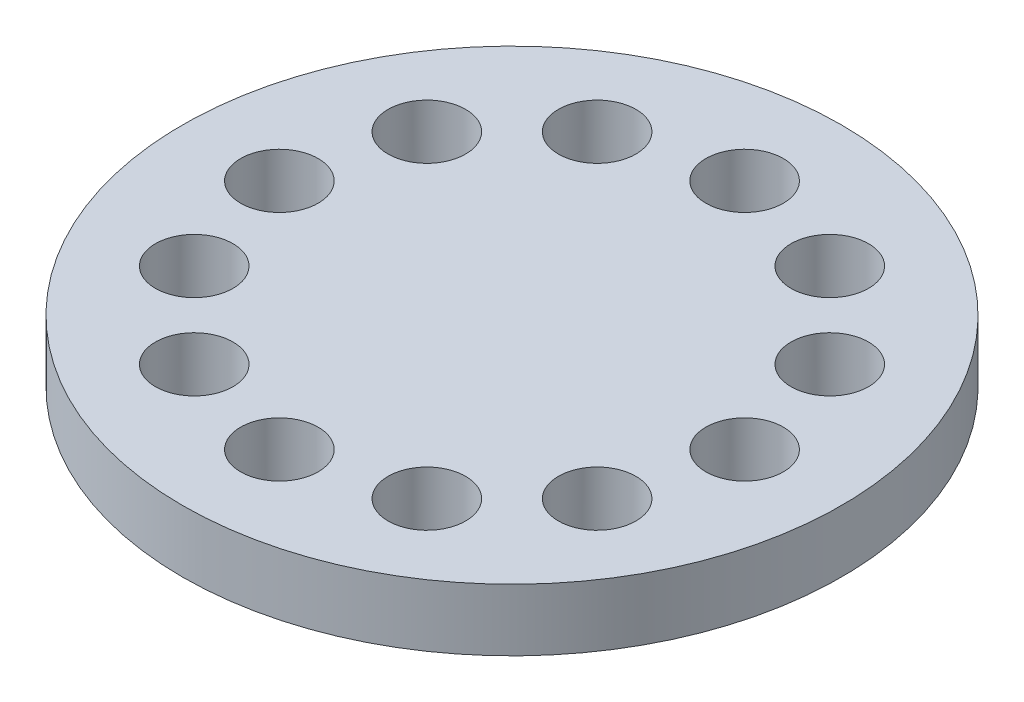
SolidWorks part; units mm, degrees
ref_plane "Front Plane" through (0, 0, 0) normal (0, 0, 1) x (1, 0, 0)
ref_plane "Top Plane" through (0, 0, 0) normal (0, 1, 0) x (1, 0, 0)
ref_plane "Right Plane" through (0, 0, 0) normal (1, 0, 0) x (0, 0, -1)
sketch "Sketch1" plane through (0, 0, 0) normal (0, 1, 0) x (1, 0, 0)
  circle A0 centre (0, 0) radius 13.4937
  dimension "D1" = 26.9875
extrude "Boss-Extrude1" add sketch "Sketch1" along normal blind 2.54
sketch "Sketch2" plane through (0, 2.54, 0) normal (0, 1, 0) x (1, 0, 0)
  line L0 (-9.525, 0) -> (0, 0) construction
  circle A0 centre (-9.525, 0) radius 1.5875
  dimension "D1" = 3.175
  dimension "D2" = 9.525
extrude "Cut-Extrude1" cut sketch "Sketch2" against normal through all both and the other way through all
ref_axis "Axis1" through (0, 2.54, 0) along (0, -1, 0)
pattern_circular "CirPattern1" count 12 over 360 about axis through (0, 2.54, 0) along (0, -1, 0) of "Cut-Extrude1"
